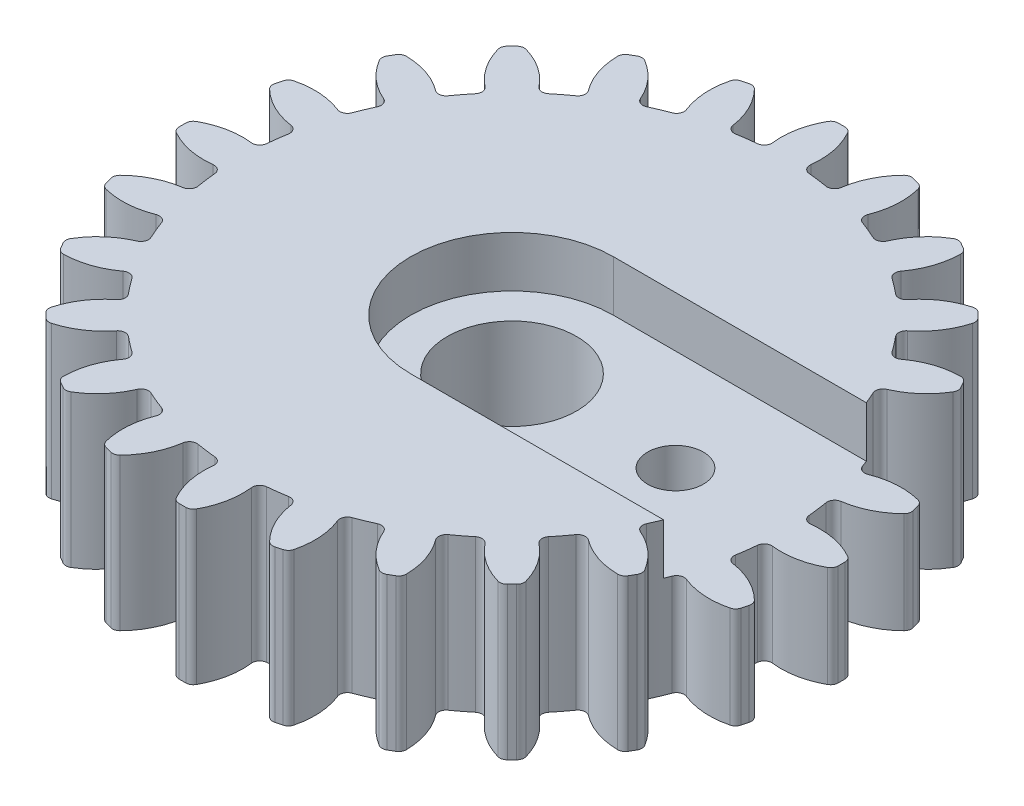
SolidWorks part; units mm, degrees
note: The reader was unsure of these and kept them because the rebuilt part matched: shared geometry of "Sketch2<5>".
ref_plane "Front Plane" through (0, 0, 0) normal (0, 0, 1) x (1, 0, 0)
ref_plane "Top Plane" through (0, 0, 0) normal (0, 1, 0) x (1, 0, 0)
ref_plane "Right Plane" through (0, 0, 0) normal (1, 0, 0) x (0, 0, -1)
sketch "Sketch2" plane through (0, 0, 0) normal (0, 1, 0) x (1, 0, 0)
  line L0 (0, 0) -> (0, 10.4648) construction
  line L1 (0.3, 13) -> (-0.3, 13)
  circle A0 centre (0, 0) radius 10.75
  circle A1 centre (0, 0) radius 13 construction
  arc A2 (-0.3, 13) -> (-0.7, 10.7272) centre (2.2248, 11.3841) ccw
  arc A3 (0.3, 13) -> (0.7, 10.7272) centre (-2.2248, 11.3841) cw
  circle A4 centre (0, 0) radius 2.55
  arc A5 (-0.7, 10.7272) -> (0.7, 10.7272) centre (0, 0) cw
  point P10 (0, 13)
  dimension "D1" = 21.5
  dimension "D2" = 26
  dimension "D5" = 5.1
  dimension "D3" = 0.6
  dimension "D4" = 0.7
extrude "Boss-Extrude1" add sketch "Sketch2" along normal blind 6
extrude "Boss-Extrude2" add sketch "Sketch2<5>" along normal blind 6 contours A3 L1 A2 A0
sketch "Sketch2<5>" plane through (0, 0, 0) normal (0, 1, 0) x (1, 0, 0) same geometry as "Sketch2"
pattern_circular "CirPattern2" count 24 over 360 about axis through (0, 0, 0) along (0, 1, 0) of "Boss-Extrude2"
fillet "Fillet1" radius 0.3 96 edges at (4.7574, 3, 9.64) (6.2402, 3, 11.4083) (6.7598, 3, 11.1083) (5.9698, 3, 8.94) (2.1003, 3, 10.5428) (3.0749, 3, 12.6347) (3.6544, 3, 12.4794) (3.4525, 3, 10.1805) (-0.7, 3, 10.7272) (-0.3, 3, 13) (0.3, 3, 13) (0.7, 3, 10.7272) (0.7, 3, -10.7272) (-3.4525, 3, 10.1805) (-3.6544, 3, 12.4794) (-3.0749, 3, 12.6347) (-2.1003, 3, 10.5428) (0.3, 3, -13) (-0.3, 3, -13) (-5.9698, 3, 8.94) (-6.7598, 3, 11.1083) (-6.2402, 3, 11.4083) (-4.7574, 3, 9.64) (-0.7, 3, -10.7272) (-8.0802, 3, 7.0903) (-9.4045, 3, 8.9803) (-8.9803, 3, 9.4045) (-7.0903, 3, 8.0802) (-9.64, 3, 4.7574) (-11.4083, 3, 6.2402) (-11.1083, 3, 6.7598) (-8.94, 3, 5.9698) (-10.5428, 3, 2.1003) (-12.6347, 3, 3.0749) (-12.4794, 3, 3.6544) (-10.1805, 3, 3.4525) (-10.7272, 3, -0.7) (-13, 3, -0.3) (-13, 3, 0.3) (-10.7272, 3, 0.7) (-10.1805, 3, -3.4525) (-12.4794, 3, -3.6544) (-12.6347, 3, -3.0749) (-10.5428, 3, -2.1003) (-8.94, 3, -5.9698) (-11.1083, 3, -6.7598) (-11.4083, 3, -6.2402) (-9.64, 3, -4.7574) (-7.0903, 3, -8.0802) (-8.9803, 3, -9.4045) (-9.4045, 3, -8.9803) (-8.0802, 3, -7.0903) (-4.7574, 3, -9.64) (-6.2402, 3, -11.4083) (-6.7598, 3, -11.1083) (-5.9698, 3, -8.94) (10.7272, 3, 0.7) (13, 3, 0.3) (13, 3, -0.3) (10.7272, 3, -0.7) (10.5428, 3, -2.1003) (12.6347, 3, -3.0749) (12.4794, 3, -3.6544) (10.1805, 3, -3.4525) (9.64, 3, -4.7574) (11.4083, 3, -6.2402) (11.1083, 3, -6.7598) (8.94, 3, -5.9698) (8.0802, 3, -7.0903) (9.4045, 3, -8.9803) (8.9803, 3, -9.4045) (7.0903, 3, -8.0802) (5.9698, 3, -8.94) (6.7598, 3, -11.1083) (6.2402, 3, -11.4083) (4.7574, 3, -9.64) (3.4525, 3, -10.1805) (3.6544, 3, -12.4794) (3.0749, 3, -12.6347) (2.1003, 3, -10.5428) (-2.1003, 3, -10.5428) (-3.0749, 3, -12.6347) (-3.6544, 3, -12.4794) (-3.4525, 3, -10.1805) (10.1805, 3, 3.4525) (12.4794, 3, 3.6544) (12.6347, 3, 3.0749) (10.5428, 3, 2.1003) (8.94, 3, 5.9698) (11.1083, 3, 6.7598) (11.4083, 3, 6.2402) (9.64, 3, 4.7574) (7.0903, 3, 8.0802) (8.9803, 3, 9.4045) (9.4045, 3, 8.9803) (8.0802, 3, 7.0903)
sketch "Sketch3" plane through (0, 6, 0) normal (0, 1, 0) x (1, 0, 0)
  line L0 (0, 0) -> (6.45, 0) construction
  circle A0 centre (6.45, 0) radius 1.1
  dimension "D1" = 2.2
  dimension "D2" = 6.45
extrude "Cut-Extrude1" cut sketch "Sketch3" against normal blind 10
sketch "Sketch4" plane through (0, 6, 0) normal (0, 1, 0) x (1, 0, 0)
  line L0 (0, 0) -> (6.4987, 0) construction
  line L1 (0, 4) -> (16.2485, 4)
  line L2 (16.2485, 4) -> (16.2485, -4)
  line L3 (16.2485, -4) -> (0, -4)
  arc A0 (0, 4) -> (0, -4) centre (0, 0) ccw
  dimension "D1" = 8
  dimension "D2" = 8
extrude "Cut-Extrude2" cut sketch "Sketch4" against normal blind 2
